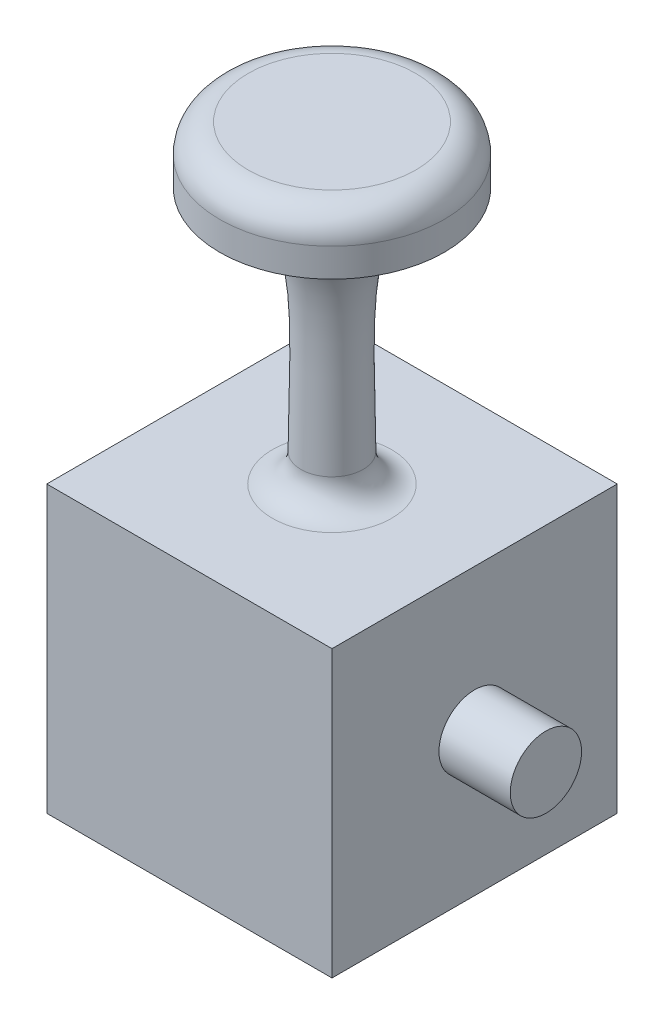
SolidWorks part; units mm, degrees
ref_plane "Front Plane" through (0, 0, 0) normal (0, 0, 1) x (1, 0, 0)
ref_plane "Top Plane" through (0, 0, 0) normal (0, 1, 0) x (1, 0, 0)
ref_plane "Right Plane" through (0, 0, 0) normal (1, 0, 0) x (0, 0, -1)
sketch "Sketch2" plane through (0, 0, 0) normal (1, 0, 0) x (0, 0, -1)
  line L1 (0, 0) -> (25.4, 0)
  line L2 (0, 0) -> (0, 25.4)
  line L3 (0, 25.4) -> (25.4, 25.4)
  line L4 (25.4, 0) -> (25.4, 25.4)
  dimension "D1" = 25.4
  dimension "D2" = 25.4
extrude "central box" add sketch "Sketch2" along normal blind 25.4
ref_point "center for extrusion of nibbles"
sketch "Sketch4" plane through (25.4, 0, 0) normal (1, 0, 0) x (0, 0, -1)
  circle A0 centre (12.7, 12.7) radius 3.175
  dimension "D1" = 6.35
extrude "nibbles" add sketch "Sketch4" along normal blind 6.35 and the other way blind 31.75
ref_point "stick extrusion spot"
ref_plane "stick drawin' plane" through (0, 0, -12.7) normal (0, 0, 1) x (1, 0, 0)
sketch "Sketch6" plane through (0, 0, -12.7) normal (0, 0, 1) x (1, 0, 0)
  line L0 (12.7, 25.4) -> (12.7, 53.34)
  line L1 (12.7, 53.34) -> (22.6999, 53.34)
  line L2 (22.6999, 53.34) -> (22.6999, 48.26)
  line L3 (12.7, 25.4) -> (15.494, 25.4)
  spline S0 degree 3 poles (22.6999, 48.26) (14.0117, 48.3515) (15.3891, 40.6548) (15.494, 25.4) knots 0 0 0 0 1 1 1 1
  dimension "D1" = 2.794
  dimension "D2" = 27.94
  dimension "D3" = 5.08
revolve "stick" add sketch "Sketch6" angle 360 about L0
fillet "yay, rounded" radius 2.54 2 edges at (12.7, 25.4, -15.494) (12.7, 53.34, -22.6999)
